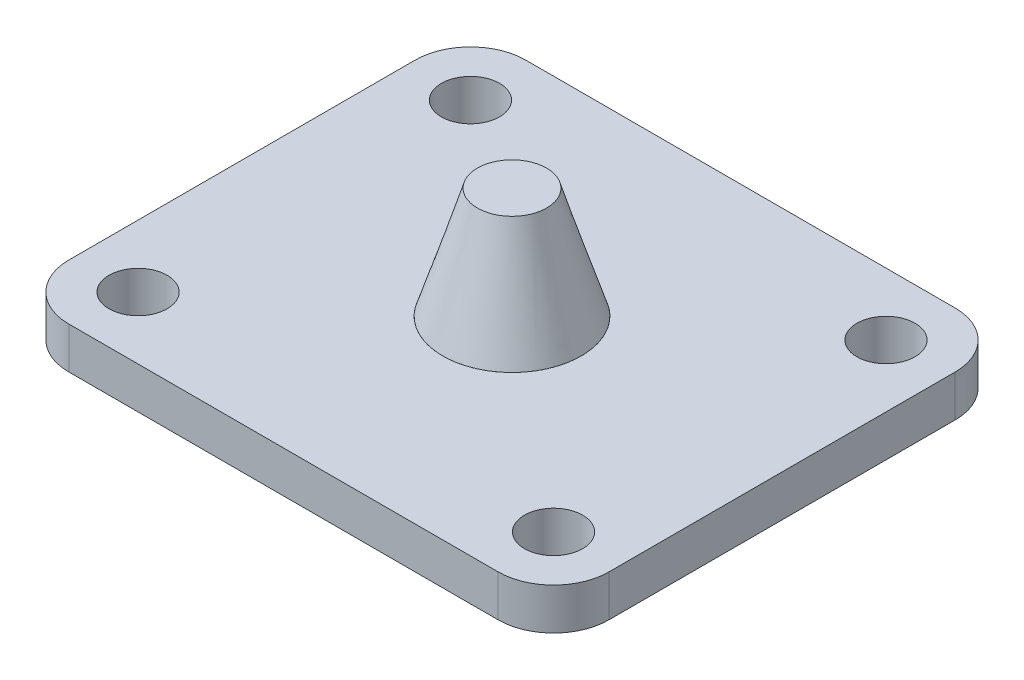
SolidWorks part; units mm, degrees
ref_plane "前视基准面" through (0, 0, 0) normal (0, 0, 1) x (1, 0, 0)
ref_plane "上视基准面" through (0, 0, 0) normal (0, 1, 0) x (1, 0, 0)
ref_plane "右视基准面" through (0, 0, 0) normal (1, 0, 0) x (0, 0, -1)
sketch "草图1" plane through (0, 0, 0) normal (0, 1, 0) x (1, 0, 0)
  line L1 (0, 0) -> (39, 0)
  line L2 (0, 0) -> (0, 33)
  line L3 (0, 33) -> (39, 33)
  line L4 (39, 0) -> (39, 33)
  line L5 (4.5, 28.5) -> (34.5, 28.5) construction
  line L6 (4.5, 28.5) -> (4.5, 4.5) construction
  line L7 (4.5, 4.5) -> (34.5, 4.5) construction
  line L8 (34.5, 28.5) -> (34.5, 4.5) construction
  circle A0 centre (4.5, 28.5) radius 2.1
  circle A1 centre (34.5, 28.5) radius 2.1
  circle A2 centre (34.5, 4.5) radius 2.1
  circle A3 centre (4.5, 4.5) radius 2.1
  point P11 (4.1259, 4.5)
  point P12 (34.8747, 28.5)
  dimension "D7" = 4.2
  dimension "D1" = 33
  dimension "D2" = 39
  dimension "D3" = 30
  dimension "D4" = 24
  dimension "D5" = 4.5
  dimension "D6" = 4.5
  dimension "D8" = 2
  dimension "D9" = 2
extrude "凸台-拉伸1" add sketch "草图1" along normal blind 3
fillet "圆角1" radius 4 4 edges at (0, 1.5, 0) (0, 1.5, -33) (39, 1.5, -33) (39, 1.5, 0)
sketch "草图2" plane through (0, 3, 0) normal (0, 1, 0) x (1, 0, 0)
  line L1 (0, 16.5) -> (39, 16.5) construction
  line L2 (0, 29) -> (0, 4) construction
  line L3 (39, 4) -> (39, 29) construction
  circle A0 centre (19.5, 16.5) radius 5
  point P4 (19.5, 16.5)
  dimension "D1" = 10
extrude "切除-拉伸1" cut sketch "草图2" against normal blind 3
ref_plane "基准面1" through (0, 11, 0) normal (0, 1, 0) x (1, 0, 0)
sketch "草图3" plane through (0, 11, 0) normal (0, 1, 0) x (1, 0, 0)
  circle A0 centre (19.5, 16.5) radius 2.5
  dimension "D1" = 5
sketch "草图4" plane through (0, 3, 0) normal (0, 1, 0) x (1, 0, 0)
  circle A0 centre (19.5, 16.5) radius 5
  dimension "D1" = 10
loft "放样1" add profiles "草图4", "草图3" connector at (23.7941, 3, -13.9386) connector at (21.8872, 11, -15.7574)
